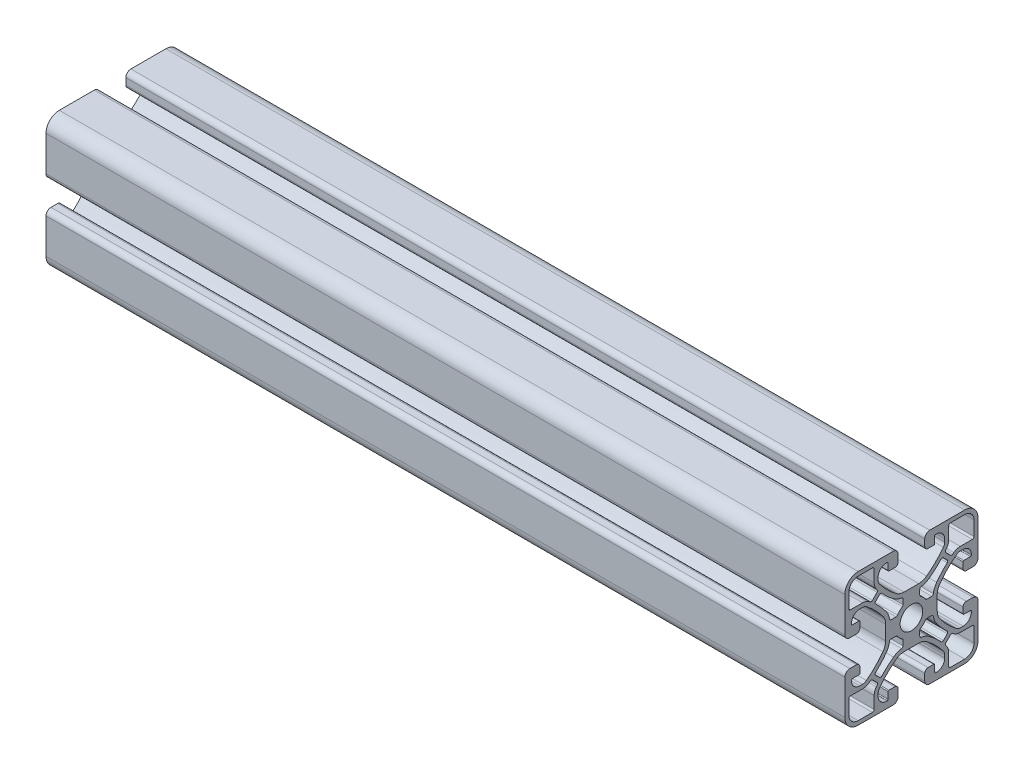
SolidWorks part; units mm, degrees
ref_plane "Front Plane" through (0, 0, 0) normal (1, 0, 0) x (0, 1, 0)
ref_plane "Top Plane" through (0, 0, 0) normal (0, 0, 1) x (0, 1, 0)
ref_plane "Right Plane" through (0, 0, 0) normal (0, 1, 0) x (-1, 0, 0)
sketch "Sketch1" plane through (0, 0, 0) normal (1, 0, 0) x (0, 1, 0)
  line L0 (9.8448, 4.6378) -> (10.0126, 4.8558)
  line L1 (10.4243, 6.082) -> (10.4243, 8.3868)
  line L2 (10.7418, 8.7043) -> (13.4723, 8.7043)
  line L3 (15.2503, 6.9263) -> (15.2503, 4.1958)
  line L4 (14.9328, 3.8783) -> (12.628, 3.8783)
  line L5 (11.4018, 3.4666) -> (11.1838, 3.2989)
  line L6 (10.7635, 3.3243) -> (9.8703, 4.2176)
  line L7 (-4.559, 3.2986) -> (-4.7769, 3.4664)
  line L8 (-6.0032, 3.8781) -> (-8.308, 3.8781)
  line L9 (-8.6255, 4.1956) -> (-8.6255, 6.9261)
  line L10 (-6.8475, 8.7041) -> (-4.117, 8.7041)
  line L11 (-3.7995, 8.3866) -> (-3.7995, 6.0818)
  line L12 (-3.3878, 4.8556) -> (-3.22, 4.6376)
  line L13 (-3.2454, 4.2174) -> (-4.1387, 3.3241)
  line L14 (4.9, -0.3064) -> (4.9, 0.6387)
  line L15 (9.4106, 3.5999) -> (10.1461, 2.8644)
  line L16 (7.1849, -1.6462) -> (6.2397, -1.6462)
  line L17 (0.3853, -1.6462) -> (-0.5599, -1.6462)
  line L18 (-3.521, 2.8644) -> (-2.7855, 3.5999)
  line L19 (1.725, 0.6387) -> (1.725, -0.3064)
  line L20 (-3.2198, -11.1051) -> (-3.3876, -11.3231)
  line L21 (-3.7993, -12.5493) -> (-3.7993, -14.8542)
  line L22 (-4.1168, -15.1717) -> (-6.8473, -15.1717)
  line L23 (-8.6253, -13.3937) -> (-8.6253, -10.6632)
  line L24 (-8.3078, -10.3457) -> (-6.0029, -10.3457)
  line L25 (-4.7767, -9.934) -> (-4.5588, -9.7662)
  line L26 (-4.1385, -9.7916) -> (-3.2452, -10.6849)
  line L27 (11.184, -9.7659) -> (11.402, -9.9337)
  line L28 (12.6282, -10.3454) -> (14.933, -10.3454)
  line L29 (15.2505, -10.6629) -> (15.2505, -13.3934)
  line L30 (13.4725, -15.1714) -> (10.742, -15.1714)
  line L31 (10.4245, -14.8539) -> (10.4245, -12.5491)
  line L32 (10.0128, -11.3229) -> (9.845, -11.1049)
  line L33 (9.8705, -10.6847) -> (10.7638, -9.7914)
  line L34 (1.725, -6.1609) -> (1.725, -7.106)
  line L35 (-2.7855, -10.0672) -> (-3.521, -9.3317)
  line L36 (-0.5599, -4.8212) -> (0.3853, -4.8212)
  line L37 (6.2397, -4.8212) -> (7.1849, -4.8212)
  line L38 (10.1461, -9.3317) -> (9.4106, -10.0672)
  line L39 (4.9, -7.106) -> (4.9, -6.1609)
  line L40 (0.7725, -13.7112) -> (0.7725, -14.9812)
  line L41 (-0.9737, -13.0762) -> (0.1375, -13.0762)
  line L42 (-1.1325, -14.5049) -> (-1.1325, -13.2349)
  line L43 (-1.45, -14.6637) -> (-1.2912, -14.6637)
  line L44 (-3.0375, -12.5811) -> (-3.0375, -13.0762)
  line L45 (4.7051, -8.1549) -> (1.9199, -8.1549)
  line L46 (9.6625, -13.0762) -> (9.6625, -12.5811)
  line L47 (7.9163, -14.6637) -> (8.075, -14.6637)
  line L48 (7.7575, -13.2349) -> (7.7575, -14.5049)
  line L49 (6.4875, -13.0762) -> (7.5988, -13.0762)
  line L50 (5.8525, -14.9812) -> (5.8525, -13.7112)
  line L51 (13.4725, -15.9337) -> (6.805, -15.9337)
  line L52 (16.0125, -6.7262) -> (16.0125, -13.3937)
  line L53 (13.79, -5.7737) -> (15.06, -5.7737)
  line L54 (13.155, -7.5199) -> (13.155, -6.4087)
  line L55 (14.5838, -7.6787) -> (13.3138, -7.6787)
  line L56 (14.7425, -7.9962) -> (14.7425, -7.8374)
  line L57 (12.6599, -9.5837) -> (13.155, -9.5837)
  line L58 (8.2338, -1.8411) -> (8.2338, -4.6262)
  line L59 (13.155, 3.1163) -> (12.6599, 3.1163)
  line L60 (14.7425, 1.3701) -> (14.7425, 1.5288)
  line L61 (13.3138, 1.2113) -> (14.5838, 1.2113)
  line L62 (13.155, -0.0587) -> (13.155, 1.0526)
  line L63 (15.06, -0.6937) -> (13.79, -0.6937)
  line L64 (16.0125, 6.9263) -> (16.0125, 0.2588)
  line L65 (6.805, 9.4663) -> (13.4725, 9.4663)
  line L66 (5.8525, 7.2438) -> (5.8525, 8.5138)
  line L67 (7.5988, 6.6088) -> (6.4875, 6.6088)
  line L68 (7.7575, 8.0376) -> (7.7575, 6.7676)
  line L69 (8.075, 8.1963) -> (7.9163, 8.1963)
  line L70 (9.6625, 6.1138) -> (9.6625, 6.6088)
  line L71 (1.9199, 1.6876) -> (4.7051, 1.6876)
  line L72 (-3.0375, 6.6088) -> (-3.0375, 6.1138)
  line L73 (-1.2912, 8.1963) -> (-1.45, 8.1963)
  line L74 (-1.1325, 6.7676) -> (-1.1325, 8.0376)
  line L75 (0.1375, 6.6088) -> (-0.9737, 6.6088)
  line L76 (0.7725, 8.5138) -> (0.7725, 7.2438)
  line L77 (-6.8475, 9.4663) -> (-0.18, 9.4663)
  line L78 (-9.3875, 0.2588) -> (-9.3875, 6.9263)
  line L79 (-7.165, -0.6937) -> (-8.435, -0.6937)
  line L80 (-6.53, 1.0526) -> (-6.53, -0.0587)
  line L81 (-7.9587, 1.2113) -> (-6.6887, 1.2113)
  line L82 (-8.1175, 1.5288) -> (-8.1175, 1.3701)
  line L83 (-6.0349, 3.1163) -> (-6.53, 3.1163)
  line L84 (-1.6087, -4.6262) -> (-1.6087, -1.8411)
  line L85 (-6.53, -9.5837) -> (-6.0349, -9.5837)
  line L86 (-8.1175, -7.8374) -> (-8.1175, -7.9962)
  line L87 (-6.6887, -7.6787) -> (-7.9587, -7.6787)
  line L88 (-6.53, -6.4087) -> (-6.53, -7.5199)
  line L89 (-8.435, -5.7737) -> (-7.165, -5.7737)
  line L90 (-9.3875, -13.3937) -> (-9.3875, -6.7262)
  line L91 (-0.18, -15.9337) -> (-6.8475, -15.9337)
  arc A0 (9.8448, 4.6378) -> (9.8703, 4.2176) centre (10.0948, 4.4421) ccw
  arc A1 (10.0126, 4.8558) -> (10.4243, 6.082) centre (8.3923, 6.082) ccw
  arc A2 (10.7418, 8.7043) -> (10.4243, 8.3868) centre (10.7418, 8.3868) ccw
  arc A3 (15.2503, 6.9263) -> (13.4723, 8.7043) centre (13.4723, 6.9263) ccw
  arc A4 (14.9328, 3.8783) -> (15.2503, 4.1958) centre (14.9328, 4.1958) ccw
  arc A5 (12.628, 3.8783) -> (11.4018, 3.4666) centre (12.628, 1.8463) ccw
  arc A6 (10.7635, 3.3243) -> (11.1838, 3.2989) centre (10.988, 3.5488) ccw
  arc A7 (-4.559, 3.2986) -> (-4.1387, 3.3241) centre (-4.3632, 3.5486) ccw
  arc A8 (-4.7769, 3.4664) -> (-6.0032, 3.8781) centre (-6.0032, 1.8461) ccw
  arc A9 (-8.6255, 4.1956) -> (-8.308, 3.8781) centre (-8.308, 4.1956) ccw
  arc A10 (-6.8475, 8.7041) -> (-8.6255, 6.9261) centre (-6.8475, 6.9261) ccw
  arc A11 (-3.7995, 8.3866) -> (-4.117, 8.7041) centre (-4.117, 8.3866) ccw
  arc A12 (-3.7995, 6.0818) -> (-3.3878, 4.8556) centre (-1.7675, 6.0818) ccw
  arc A13 (-3.2454, 4.2174) -> (-3.22, 4.6376) centre (-3.47, 4.4419) ccw
  arc A14 (5.9736, -1.5018) -> (6.2397, -1.6462) centre (6.2397, -1.3287) ccw
  arc A15 (5.9736, -1.5018) -> (5.0443, -0.5726) centre (3.3125, -3.2337) ccw
  arc A16 (4.9, -0.3064) -> (5.0443, -0.5726) centre (5.2175, -0.3064) ccw
  arc A17 (5.1763, 0.9535) -> (4.9, 0.6387) centre (5.2175, 0.6387) ccw
  arc A18 (5.1763, 0.9535) -> (6.7288, 1.586) centre (4.7476, 4.2276) ccw
  arc A19 (6.7288, 1.586) -> (8.9531, 3.5911) centre (-3.2534, 14.8956) ccw
  arc A20 (9.4106, 3.5999) -> (8.9531, 3.5911) centre (9.1861, 3.3754) ccw
  arc A21 (10.1373, 2.4069) -> (10.1461, 2.8644) centre (9.9215, 2.6399) ccw
  arc A22 (10.1373, 2.4069) -> (8.1322, 0.1826) centre (21.4418, -9.7996) ccw
  arc A23 (8.1322, 0.1826) -> (7.4997, -1.3699) centre (10.7738, -1.7986) ccw
  arc A24 (7.1849, -1.6462) -> (7.4997, -1.3699) centre (7.1849, -1.3287) ccw
  arc A25 (1.5807, -0.5726) -> (1.725, -0.3064) centre (1.4075, -0.3064) ccw
  arc A26 (1.5807, -0.5726) -> (0.6514, -1.5018) centre (3.3125, -3.2337) ccw
  arc A27 (0.3853, -1.6462) -> (0.6514, -1.5018) centre (0.3853, -1.3287) ccw
  arc A28 (-0.8747, -1.3699) -> (-0.5599, -1.6462) centre (-0.5599, -1.3287) ccw
  arc A29 (-0.8747, -1.3699) -> (-1.5071, 0.1826) centre (-4.1487, -1.7986) ccw
  arc A30 (-1.5071, 0.1826) -> (-3.5122, 2.4069) centre (-14.8167, -9.7996) ccw
  arc A31 (-3.521, 2.8644) -> (-3.5122, 2.4069) centre (-3.2965, 2.6399) ccw
  arc A32 (-2.3281, 3.5911) -> (-2.7855, 3.5999) centre (-2.561, 3.3754) ccw
  arc A33 (-2.3281, 3.5911) -> (-0.1038, 1.586) centre (9.8784, 14.8956) ccw
  arc A34 (-0.1038, 1.586) -> (1.4487, 0.9535) centre (1.8774, 4.2276) ccw
  arc A35 (1.725, 0.6387) -> (1.4487, 0.9535) centre (1.4075, 0.6387) ccw
  arc A36 (-3.2198, -11.1051) -> (-3.2452, -10.6849) centre (-3.4697, -10.9094) ccw
  arc A37 (-3.3876, -11.3231) -> (-3.7993, -12.5493) centre (-1.7673, -12.5493) ccw
  arc A38 (-4.1168, -15.1717) -> (-3.7993, -14.8542) centre (-4.1168, -14.8542) ccw
  arc A39 (-8.6253, -13.3937) -> (-6.8473, -15.1717) centre (-6.8473, -13.3937) ccw
  arc A40 (-8.3078, -10.3457) -> (-8.6253, -10.6632) centre (-8.3078, -10.6632) ccw
  arc A41 (-6.0029, -10.3457) -> (-4.7767, -9.934) centre (-6.0029, -8.3137) ccw
  arc A42 (-4.1385, -9.7916) -> (-4.5588, -9.7662) centre (-4.363, -10.0161) ccw
  arc A43 (11.184, -9.7659) -> (10.7638, -9.7914) centre (10.9883, -10.0159) ccw
  arc A44 (11.402, -9.9337) -> (12.6282, -10.3454) centre (12.6282, -8.3134) ccw
  arc A45 (15.2505, -10.6629) -> (14.933, -10.3454) centre (14.933, -10.6629) ccw
  arc A46 (13.4725, -15.1714) -> (15.2505, -13.3934) centre (13.4725, -13.3934) ccw
  arc A47 (10.4245, -14.8539) -> (10.742, -15.1714) centre (10.742, -14.8539) ccw
  arc A48 (10.4245, -12.5491) -> (10.0128, -11.3229) centre (8.3925, -12.5491) ccw
  arc A49 (9.8705, -10.6847) -> (9.845, -11.1049) centre (10.095, -10.9092) ccw
  arc A50 (0.6514, -4.9655) -> (0.3853, -4.8212) centre (0.3853, -5.1387) ccw
  arc A51 (0.6514, -4.9655) -> (1.5807, -5.8947) centre (3.3125, -3.2337) ccw
  arc A52 (1.725, -6.1609) -> (1.5807, -5.8947) centre (1.4075, -6.1609) ccw
  arc A53 (1.4487, -7.4208) -> (1.725, -7.106) centre (1.4075, -7.106) ccw
  arc A54 (1.4487, -7.4208) -> (-0.1038, -8.0533) centre (1.8774, -10.6949) ccw
  arc A55 (-0.1038, -8.0533) -> (-2.3281, -10.0584) centre (9.8784, -21.3629) ccw
  arc A56 (-2.7855, -10.0672) -> (-2.3281, -10.0584) centre (-2.561, -9.8427) ccw
  arc A57 (-3.5122, -8.8742) -> (-3.521, -9.3317) centre (-3.2965, -9.1072) ccw
  arc A58 (-3.5122, -8.8742) -> (-1.5071, -6.65) centre (-14.8167, 3.3322) ccw
  arc A59 (-1.5071, -6.65) -> (-0.8747, -5.0974) centre (-4.1487, -4.6688) ccw
  arc A60 (-0.5599, -4.8212) -> (-0.8747, -5.0974) centre (-0.5599, -5.1387) ccw
  arc A61 (5.0443, -5.8947) -> (4.9, -6.1609) centre (5.2175, -6.1609) ccw
  arc A62 (5.0443, -5.8947) -> (5.9736, -4.9655) centre (3.3125, -3.2337) ccw
  arc A63 (6.2397, -4.8212) -> (5.9736, -4.9655) centre (6.2397, -5.1387) ccw
  arc A64 (7.4997, -5.0974) -> (7.1849, -4.8212) centre (7.1849, -5.1387) ccw
  arc A65 (7.4997, -5.0974) -> (8.1322, -6.65) centre (10.7738, -4.6688) ccw
  arc A66 (8.1322, -6.65) -> (10.1373, -8.8742) centre (21.4418, 3.3322) ccw
  arc A67 (10.1461, -9.3317) -> (10.1373, -8.8742) centre (9.9215, -9.1072) ccw
  arc A68 (8.9531, -10.0584) -> (9.4106, -10.0672) centre (9.1861, -9.8427) ccw
  arc A69 (8.9531, -10.0584) -> (6.7288, -8.0533) centre (-3.2534, -21.3629) ccw
  arc A70 (6.7288, -8.0533) -> (5.1763, -7.4208) centre (4.7476, -10.6949) ccw
  arc A71 (4.9, -7.106) -> (5.1763, -7.4208) centre (5.2175, -7.106) ccw
  circle A72 centre (3.3125, -3.2337) radius 2.159
  arc A73 (-0.18, -15.9337) -> (0.7725, -14.9812) centre (-0.18, -14.9812) ccw
  arc A74 (0.7725, -13.7112) -> (0.1375, -13.0762) centre (0.1375, -13.7112) ccw
  arc A75 (-0.9737, -13.0762) -> (-1.1325, -13.2349) centre (-0.9737, -13.2349) ccw
  arc A76 (-1.2912, -14.6637) -> (-1.1325, -14.5049) centre (-1.2912, -14.5049) ccw
  arc A77 (-3.0375, -13.0762) -> (-1.45, -14.6637) centre (-1.45, -13.0762) ccw
  arc A78 (-2.7802, -11.8147) -> (-3.0375, -12.5811) centre (-1.7675, -12.5811) ccw
  arc A79 (0.404, -8.6569) -> (-2.7802, -11.8147) centre (9.8784, -21.3947) ccw
  arc A80 (1.9199, -8.1549) -> (0.404, -8.6569) centre (1.9199, -10.6949) ccw
  arc A81 (6.221, -8.6569) -> (4.7051, -8.1549) centre (4.7051, -10.6949) ccw
  arc A82 (9.4052, -11.8147) -> (6.221, -8.6569) centre (-3.2534, -21.3947) ccw
  arc A83 (9.6625, -12.5811) -> (9.4052, -11.8147) centre (8.3925, -12.5811) ccw
  arc A84 (8.075, -14.6637) -> (9.6625, -13.0762) centre (8.075, -13.0762) ccw
  arc A85 (7.7575, -14.5049) -> (7.9163, -14.6637) centre (7.9163, -14.5049) ccw
  arc A86 (7.7575, -13.2349) -> (7.5988, -13.0762) centre (7.5988, -13.2349) ccw
  arc A87 (6.4875, -13.0762) -> (5.8525, -13.7112) centre (6.4875, -13.7112) ccw
  arc A88 (5.8525, -14.9812) -> (6.805, -15.9337) centre (6.805, -14.9812) ccw
  arc A89 (13.4725, -15.9337) -> (16.0125, -13.3937) centre (13.4725, -13.3937) ccw
  arc A90 (16.0125, -6.7262) -> (15.06, -5.7737) centre (15.06, -6.7262) ccw
  arc A91 (13.79, -5.7737) -> (13.155, -6.4087) centre (13.79, -6.4087) ccw
  arc A92 (13.155, -7.5199) -> (13.3138, -7.6787) centre (13.3138, -7.5199) ccw
  arc A93 (14.7425, -7.8374) -> (14.5838, -7.6787) centre (14.5838, -7.8374) ccw
  arc A94 (13.155, -9.5837) -> (14.7425, -7.9962) centre (13.155, -7.9962) ccw
  arc A95 (11.8936, -9.3263) -> (12.6599, -9.5837) centre (12.6599, -8.3137) ccw
  arc A96 (8.7357, -6.1421) -> (11.8936, -9.3263) centre (21.4735, 3.3322) ccw
  arc A97 (8.2338, -4.6262) -> (8.7357, -6.1421) centre (10.7738, -4.6262) ccw
  arc A98 (8.7357, -0.3252) -> (8.2338, -1.8411) centre (10.7738, -1.8411) ccw
  arc A99 (11.8936, 2.859) -> (8.7357, -0.3252) centre (21.4735, -9.7996) ccw
  arc A100 (12.6599, 3.1163) -> (11.8936, 2.859) centre (12.6599, 1.8463) ccw
  arc A101 (14.7425, 1.5288) -> (13.155, 3.1163) centre (13.155, 1.5288) ccw
  arc A102 (14.5838, 1.2113) -> (14.7425, 1.3701) centre (14.5838, 1.3701) ccw
  arc A103 (13.3138, 1.2113) -> (13.155, 1.0526) centre (13.3138, 1.0526) ccw
  arc A104 (13.155, -0.0587) -> (13.79, -0.6937) centre (13.79, -0.0587) ccw
  arc A105 (15.06, -0.6937) -> (16.0125, 0.2588) centre (15.06, 0.2588) ccw
  arc A106 (16.0125, 6.9263) -> (13.4725, 9.4663) centre (13.4725, 6.9263) ccw
  arc A107 (6.805, 9.4663) -> (5.8525, 8.5138) centre (6.805, 8.5138) ccw
  arc A108 (5.8525, 7.2438) -> (6.4875, 6.6088) centre (6.4875, 7.2438) ccw
  arc A109 (7.5988, 6.6088) -> (7.7575, 6.7676) centre (7.5988, 6.7676) ccw
  arc A110 (7.9163, 8.1963) -> (7.7575, 8.0376) centre (7.9163, 8.0376) ccw
  arc A111 (9.6625, 6.6088) -> (8.075, 8.1963) centre (8.075, 6.6088) ccw
  arc A112 (9.4052, 5.3474) -> (9.6625, 6.1138) centre (8.3925, 6.1138) ccw
  arc A113 (6.221, 2.1896) -> (9.4052, 5.3474) centre (-3.2534, 14.9273) ccw
  arc A114 (4.7051, 1.6876) -> (6.221, 2.1896) centre (4.7051, 4.2276) ccw
  arc A115 (0.404, 2.1896) -> (1.9199, 1.6876) centre (1.9199, 4.2276) ccw
  arc A116 (-2.7802, 5.3474) -> (0.404, 2.1896) centre (9.8784, 14.9273) ccw
  arc A117 (-3.0375, 6.1138) -> (-2.7802, 5.3474) centre (-1.7675, 6.1138) ccw
  arc A118 (-1.45, 8.1963) -> (-3.0375, 6.6088) centre (-1.45, 6.6088) ccw
  arc A119 (-1.1325, 8.0376) -> (-1.2912, 8.1963) centre (-1.2912, 8.0376) ccw
  arc A120 (-1.1325, 6.7676) -> (-0.9737, 6.6088) centre (-0.9737, 6.7676) ccw
  arc A121 (0.1375, 6.6088) -> (0.7725, 7.2438) centre (0.1375, 7.2438) ccw
  arc A122 (0.7725, 8.5138) -> (-0.18, 9.4663) centre (-0.18, 8.5138) ccw
  arc A123 (-6.8475, 9.4663) -> (-9.3875, 6.9263) centre (-6.8475, 6.9263) ccw
  arc A124 (-9.3875, 0.2588) -> (-8.435, -0.6937) centre (-8.435, 0.2588) ccw
  arc A125 (-7.165, -0.6937) -> (-6.53, -0.0587) centre (-7.165, -0.0587) ccw
  arc A126 (-6.53, 1.0526) -> (-6.6887, 1.2113) centre (-6.6887, 1.0526) ccw
  arc A127 (-8.1175, 1.3701) -> (-7.9587, 1.2113) centre (-7.9587, 1.3701) ccw
  arc A128 (-6.53, 3.1163) -> (-8.1175, 1.5288) centre (-6.53, 1.5288) ccw
  arc A129 (-5.2685, 2.859) -> (-6.0349, 3.1163) centre (-6.0349, 1.8463) ccw
  arc A130 (-2.1107, -0.3252) -> (-5.2685, 2.859) centre (-14.8485, -9.7996) ccw
  arc A131 (-1.6087, -1.8411) -> (-2.1107, -0.3252) centre (-4.1487, -1.8411) ccw
  arc A132 (-2.1107, -6.1421) -> (-1.6087, -4.6262) centre (-4.1487, -4.6262) ccw
  arc A133 (-5.2685, -9.3263) -> (-2.1107, -6.1421) centre (-14.8485, 3.3322) ccw
  arc A134 (-6.0349, -9.5837) -> (-5.2685, -9.3263) centre (-6.0349, -8.3137) ccw
  arc A135 (-8.1175, -7.9962) -> (-6.53, -9.5837) centre (-6.53, -7.9962) ccw
  arc A136 (-7.9587, -7.6787) -> (-8.1175, -7.8374) centre (-7.9587, -7.8374) ccw
  arc A137 (-6.6887, -7.6787) -> (-6.53, -7.5199) centre (-6.6887, -7.5199) ccw
  arc A138 (-6.53, -6.4087) -> (-7.165, -5.7737) centre (-7.165, -6.4087) ccw
  arc A139 (-8.435, -5.7737) -> (-9.3875, -6.7262) centre (-8.435, -6.7262) ccw
  arc A140 (-9.3875, -13.3937) -> (-6.8475, -15.9337) centre (-6.8475, -13.3937) ccw
  dimension "D1" = 25.4
extrude "Boss-Extrude1" add sketch "Sketch1" along normal blind 152.4
